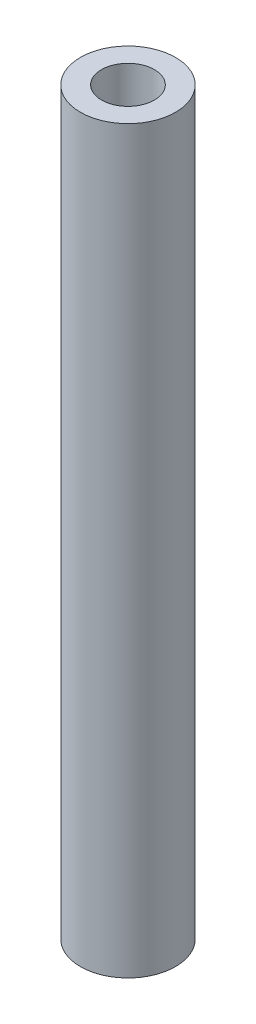
SolidWorks part; units mm, degrees
ref_plane "Front Plane" through (0, 0, 0) normal (0, 0, 1) x (1, 0, 0)
ref_plane "Top Plane" through (0, 0, 0) normal (0, 1, 0) x (1, 0, 0)
ref_plane "Right Plane" through (0, 0, 0) normal (1, 0, 0) x (0, 0, -1)
sketch "Sketch1" plane through (0, 0, 0) normal (0, 1, 0) x (1, 0, 0)
  circle A0 centre (0, 0) radius 2.25
  circle A1 centre (0, 0) radius 1.25
  dimension "D1" = 2.5
  dimension "D2" = 4.5
extrude "Boss-Extrude1" add sketch "Sketch1" along normal blind 35
